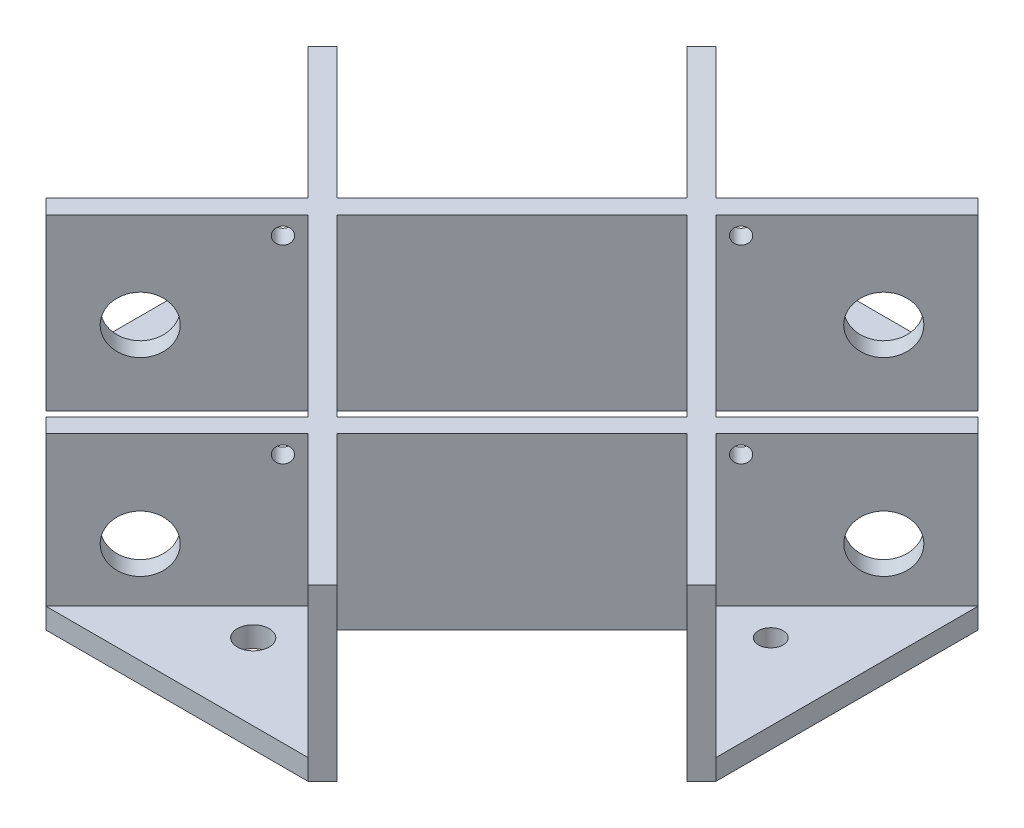
SolidWorks part; units mm, degrees
material "Windform GT"
ref_plane "Front Plane" through (0, 0, 0) normal (0, 0, 1) x (1, 0, 0)
ref_plane "Top Plane" through (0, 0, 0) normal (0, 1, 0) x (1, 0, 0)
ref_plane "Right Plane" through (0, 0, 0) normal (1, 0, 0) x (0, 0, -1)
ref_axis "Axis1" through (0, 2.1, 0) along (0, -1, 0)
sketch "Usable Space" plane through (0, 0, 0) normal (0, 1, 0) x (1, 0, 0)
  line L1 (-32.5, -32.5) -> (32.5, -32.5) construction
  line L2 (-32.5, -32.5) -> (-32.5, 32.5) construction
  line L3 (-32.5, 32.5) -> (32.5, 32.5) construction
  line L4 (32.5, -32.5) -> (32.5, 32.5) construction
  line L5 (-32.5, -32.5) -> (32.5, 32.5) construction
  line L6 (-32.5, 32.5) -> (32.5, -32.5) construction
  point P0 (0, 0)
  dimension "D1" = 65
sketch "Sketch3" plane through (0, 0, 0) normal (0, 1, 0) x (1, 0, 0)
  line L0 (-32.5, -12.701) -> (-12.701, -32.5)
  line L1 (-32.5, -32.5) -> (-32.5, 32.5) construction
  line L2 (-12.701, -32.5) -> (0, -19.799)
  line L3 (-32.5, -32.5) -> (32.5, 32.5) construction
  line L4 (0, -19.799) -> (0, 0)
  line L5 (0, 0) -> (-19.799, 0)
  line L7 (-19.799, 0) -> (-32.5, -12.701)
  line L8 (-32.5, -32.5) -> (32.5, -32.5) construction
  dimension "D1" = 28
extrude "General shape" add sketch "Sketch3" along normal blind 2
sketch "Sketch4" plane through (0, 2, 0) normal (0, 1, 0) x (1, 0, 0)
  line L0 (-19.799, 0) -> (-32.5, -12.701)
  line L1 (-19.799, 0) -> (-32.5, -12.701) construction
  line L2 (-32.5, -12.701) -> (-31.0858, -14.1152)
  line L3 (-31.0858, -14.1152) -> (-16.9706, 0)
  line L4 (0, 0) -> (-19.799, 0) construction
  line L5 (-16.9706, 0) -> (-19.799, 0)
  line L6 (-22.6005, -22.6005) -> (0, 0) construction
  line L7 (-32.5, -12.701) -> (-12.701, -32.5) construction
  line L8 (-14.1152, -31.0858) -> (0, -16.9706)
  line L9 (-12.701, -32.5) -> (-14.1152, -31.0858)
  line L10 (0, -19.799) -> (-12.701, -32.5)
  line L11 (0, -16.9706) -> (0, -19.799)
  dimension "D1" = 2
extrude "Retaining walls" add sketch "Sketch4" along normal blind 14.5
sketch "Sketch14" plane through (0, 0, 0) normal (0, -1, 0) x (1, 0, 0)
  line L0 (-19.799, 0) -> (-32.5, 12.701)
  line L1 (-19.799, 0) -> (-32.5, 12.701) construction
  line L2 (-32.5, 12.701) -> (-32.5, 0)
  line L3 (-32.5, 0) -> (-19.799, 0)
  line L4 (0, 19.799) -> (0, 32.5)
  line L5 (0, 32.5) -> (-12.701, 32.5)
  line L6 (-12.701, 32.5) -> (0, 19.799) construction
  line L7 (0, 19.799) -> (-12.701, 32.5)
  circle A1 centre (-29.049, 0) radius 1 construction
  dimension "D1" = 9.25
  dimension "D2" = 2
extrude "Exterior mounting edge" add sketch "Sketch14" against normal blind 2
sketch "Sketch18" plane through (0, 2, 0) normal (0, 1, 0) x (1, 0, 0)
  line L0 (-16.9706, 0) -> (0, -16.9706)
  line L1 (-18.3848, -1.4142) -> (-1.4142, -18.3848)
  line L2 (-31.0858, -14.1152) -> (-16.9706, 0) construction
  line L3 (0, -16.9706) -> (-14.1152, -31.0858) construction
  line L4 (-18.3848, -1.4142) -> (-16.9706, 0)
  line L5 (0, -16.9706) -> (-1.4142, -18.3848)
  dimension "D1" = 2
extrude "Rear wall" add sketch "Sketch18" along normal blind 14.5
sketch "Sketch19" plane through (-8.4853, 0, 8.4853) normal (0.7071, 0, -0.7071) x (-0.7071, 0, -0.7071)
  line L0 (0, 16.5) -> (0, 2) construction
  line L1 (-12, 16.5) -> (12, 16.5) construction
  line L2 (-12, 2) -> (12, 2) construction
  point P6 (0, 9.25)
fillet "Fillet13" [suppressed] radius 1
ref_plane "Plane2" [suppressed] through (0, 0, 0) normal (0.7071, 0, 0.7071) x (0.7071, 0, -0.7071)
sketch "Sketch35" plane through (-9.8995, 0, -9.8995) normal (-0.7071, 0, -0.7071) x (-0.7071, 0, 0.7071)
  line L0 (25.5, 16.5) -> (25.5, 2) construction
  line L2 (14, 16.5) -> (14, 2) construction
  line L3 (14, 2) -> (31.9619, 2) construction
  line L4 (15.7119, 16.5) -> (15.7119, 2) construction
  line L5 (14, 16.5) -> (31.9619, 16.5) construction
  line L6 (14, 2) -> (31.9619, 2) construction
  line L7 (14, 16.5) -> (31.9619, 16.5) construction
  line L8 (31.9619, 16.5) -> (31.9619, 2) construction
  circle A0 centre (25.5, 7.25) radius 2.75
  circle A1 centre (15.7119, 14.75) radius 0.8
  point P14 (0, 0)
  point P17 (0, 0)
  point P22 (0, 0)
  point P23 (0, 0)
  dimension "D1" = 5.5
  dimension "D4" = 1.6
  dimension "D5" = 1.75
  dimension "D6" = 9.25
  dimension "D2" = 11.5
  dimension "D3" = 16.25
extrude "Cut-Extrude2" cut sketch "Sketch35" against normal through all both and the other way through all
pattern_circular "CirPattern2" count 4 over 360 about axis through (0, 2.1, 0) along (0, -1, 0) of "General shape", "Retaining walls"
combine bodies "Combine1" operation type add bodies to combine 104 111 110 139
sketch "Exterior mounting hole location" plane through (0, 2, 0) normal (0, 1, 0) x (1, 0, 0)
  line L0 (-32.5, 0) -> (-19.799, 0) construction
  line L1 (-32.5, -12.701) -> (-32.5, 12.701) construction
  point P5 (-25.1, 0)
  point P7 (0, 25.1)
  point P13 (25.1, 0)
  point P14 (0, -25.1)
  dimension "D1" = 4
  dimension "D2" = 25.1
hole_wizard "Exterior mounting hole" positions "Sketch16" profile "Sketch17" hole size "M2" standard "ANSI Metric" end condition up to next
sketch "Sketch16" plane through (0, 2, 0) normal (0, 1, 0) x (1, 0, 0)
  point P0 (-25.1, 0)
  point P15 (25.1, 0)
sketch "Sketch17" plane through (-25.1, 2, 0) normal (1, 0, 0) x (0, 0, 1)
  line L0 (0, 0) -> (0, 2)
  line L1 (0, 2) -> (1.2, 2)
  line L2 (1.2, 2) -> (1.2, 0)
  line L5 (1.2, 0) -> (0, 0)
  line L11 (0, -6.35) -> (0, 107.95) construction
  dimension "Thru Hole Dia." = 2.4
  dimension "Thru Hole Depth" = 2
hole_wizard "Shoulder screw mounting holes " positions "Sketch24" profile "Sketch25" hole size "M2.5" standard "ANSI Metric" end condition up to next
sketch "Sketch24" plane through (0, 2, 0) normal (0, 1, 0) x (1, 0, 0)
  point P0 (0, -25.1)
  point P3 (0, 25.1)
sketch "Sketch25" plane through (0, 2, 25.1) normal (1, 0, 0) x (0, 0, 1)
  line L0 (0, 0) -> (0, 2)
  line L1 (0, 2) -> (1.55, 2)
  line L2 (1.55, 2) -> (1.55, 0)
  line L5 (1.55, 0) -> (0, 0)
  line L11 (0, -6.35) -> (0, 107.95) construction
  dimension "Thru Hole Dia." = 3.1
  dimension "Thru Hole Depth" = 2
sketch "Sketch23" plane through (0, 2, 0) normal (0, 1, 0) x (1, 0, 0)
  line L0 (0, 16.9706) -> (-16.9706, 0)
  line L5 (-16.9706, 0) -> (0, -16.9706)
  line L6 (0, -16.9706) -> (16.9706, 0)
  line L7 (16.9706, 0) -> (0, 16.9706)
  line L8 (31.0858, 14.1152) -> (18.3848, 1.4142) construction
  line L9 (18.3848, 1.4142) -> (1.4142, 18.3848) construction
  line L10 (1.4142, 18.3848) -> (14.1152, 31.0858) construction
  line L11 (-18.3848, 1.4142) -> (-31.0858, 14.1152) construction
  line L12 (-1.4142, 18.3848) -> (-18.3848, 1.4142) construction
  line L13 (-14.1152, 31.0858) -> (-1.4142, 18.3848) construction
  line L14 (-1.4142, -18.3848) -> (-14.1152, -31.0858) construction
  line L15 (-18.3848, -1.4142) -> (-1.4142, -18.3848) construction
  line L16 (-31.0858, -14.1152) -> (-18.3848, -1.4142) construction
  line L17 (14.1152, -31.0858) -> (1.4142, -18.3848) construction
  line L18 (18.3848, -1.4142) -> (31.0858, -14.1152) construction
  line L19 (1.4142, -18.3848) -> (18.3848, -1.4142) construction
  line L20 (31.0858, 14.1152) -> (18.3848, 1.4142)
  line L21 (18.3848, 1.4142) -> (1.4142, 18.3848)
  line L22 (1.4142, 18.3848) -> (14.1152, 31.0858)
  line L23 (-18.3848, 1.4142) -> (-31.0858, 14.1152)
  line L24 (-1.4142, 18.3848) -> (-18.3848, 1.4142)
  line L25 (-14.1152, 31.0858) -> (-1.4142, 18.3848)
  line L26 (-1.4142, -18.3848) -> (-14.1152, -31.0858)
  line L27 (-18.3848, -1.4142) -> (-1.4142, -18.3848)
  line L28 (-31.0858, -14.1152) -> (-18.3848, -1.4142)
  line L29 (14.1152, -31.0858) -> (1.4142, -18.3848)
  line L30 (18.3848, -1.4142) -> (31.0858, -14.1152)
  line L31 (1.4142, -18.3848) -> (18.3848, -1.4142)
  line L32 (-14.1152, 31.0858) -> (-31.0858, 14.1152)
  line L33 (-14.1152, -31.0858) -> (-31.0858, -14.1152)
  line L34 (14.1152, -31.0858) -> (31.0858, -14.1152)
  line L35 (31.0858, 14.1152) -> (14.1152, 31.0858)
extrude "Cut-Extrude1" cut sketch "Sketch23" against normal up to next
